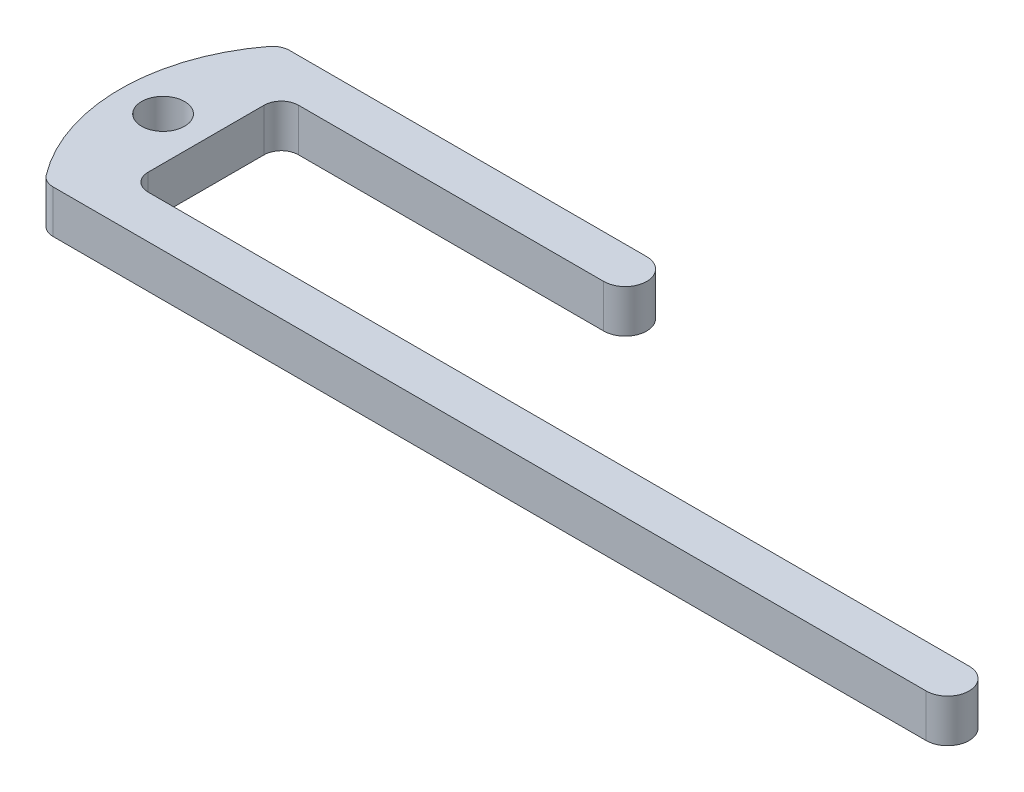
SolidWorks part; units mm, degrees
ref_plane "Front Plane" through (0, 0, 0) normal (0, 0, 1) x (1, 0, 0)
ref_plane "Top Plane" through (0, 0, 0) normal (0, 1, 0) x (1, 0, 0)
ref_plane "Right Plane" through (0, 0, 0) normal (1, 0, 0) x (0, 0, -1)
other "Bounding Box"
ref_plane "Default Plane" through (-8.9266, -12.7485, 0) normal (-0.1736, 0.9848, 0) x (0.9848, 0.1736, 0)
sketch "Sketch1" plane through (0, 0, 0) normal (0, 1, 0) x (1, 0, 0)
  line L0 (0, 0) -> (0, 28.575) construction
  line L1 (0, 28.575) -> (50.8, 28.575) construction
  line L2 (0, 0) -> (127, 0) construction
  line L3 (-3.175, 31.75) -> (50.8, 31.75)
  line L4 (-3.175, -3.175) -> (-3.175, 31.75) construction
  line L5 (-3.175, -3.175) -> (127, -3.175)
  line L6 (3.175, 25.4) -> (50.8, 25.4)
  line L7 (3.175, 3.175) -> (3.175, 25.4)
  line L8 (3.175, 3.175) -> (127, 3.175)
  line L9 (50.8, 25.4) -> (50.8, 31.75) construction
  line L10 (127, -3.175) -> (127, 3.175) construction
  line L11 (3.175, 25.4) -> (-3.175, 25.4) construction
  line L12 (-9.525, 14.2875) -> (-3.175, 14.2875) construction
  arc A0 (50.8, 31.75) -> (50.8, 25.4) centre (50.8, 28.575) cw
  arc A1 (127, 3.175) -> (127, -3.175) centre (127, 0) cw
  arc A2 (-3.175, -3.175) -> (-3.175, 31.75) centre (17.6609, 14.2875) cw
  circle A3 centre (-3.175, 14.2875) radius 3.175
  point P16 (0, 25.4)
  dimension "D5" = 6.35
  dimension "D1" = 28.575
  dimension "D2" = 50.8
  dimension "D3" = 127
  dimension "D4" = 6.35
extrude "Boss-Extrude1" add sketch "Sketch1" along normal mid plane 6.35
fillet "Fillet1" radius 2.54 4 edges at (-3.175, 0, -31.75) (-3.175, 0, 3.175) (3.175, 0, -3.175) (3.175, 0, -25.4)
